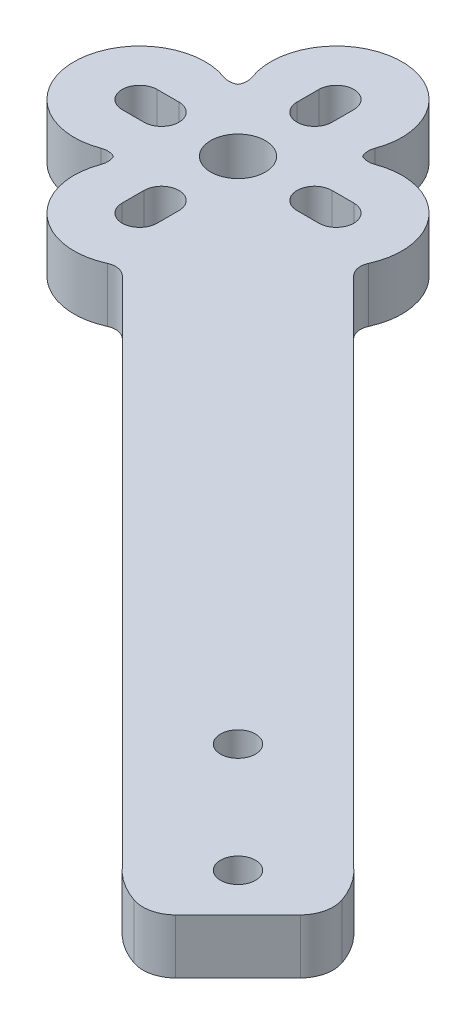
SolidWorks part; units mm, degrees
ref_plane "Front Plane" through (0, 0, 0) normal (0, 0, 1) x (1, 0, 0)
ref_plane "Top Plane" through (0, 0, 0) normal (0, 1, 0) x (1, 0, 0)
ref_plane "Right Plane" through (0, 0, 0) normal (1, 0, 0) x (0, 0, -1)
sketch "Sketch1" plane through (0, 0, 0) normal (0, 1, 0) x (1, 0, 0)
  line L0 (0, 0) -> (79.0685, 79.0685)
  line L1 (-15, 15) -> (15, 15)
  line L2 (-15, 15) -> (-15, -15)
  line L3 (-15, -15) -> (15, -15)
  line L4 (15, 15) -> (15, -15)
  line L5 (-15, 15) -> (15, -15) construction
  line L6 (-15, -15) -> (15, 15) construction
  line L7 (-22.5, 22.5) -> (22.5, 22.5)
  line L8 (-22.5, 22.5) -> (-22.5, -22.5)
  line L9 (-22.5, -22.5) -> (22.5, -22.5)
  line L10 (22.5, 22.5) -> (22.5, -22.5)
  line L11 (-22.5, 22.5) -> (22.5, -22.5) construction
  line L12 (-22.5, -22.5) -> (22.5, 22.5) construction
  line L13 (0, 0) -> (79.0685, -79.0685)
  line L14 (0, 0) -> (-79.0685, -79.0685)
  line L15 (0, 0) -> (-79.0685, 79.0685)
  line L16 (-79.0685, 79.0685) -> (-73.4117, 73.4117)
  line L17 (-79.0685, 88.0685) -> (-79.0685, 86.0685) construction
  line L22 (-77.4685, 88.0685) -> (-77.4685, 86.0685)
  line L25 (-80.6685, 88.0685) -> (-80.6685, 86.0685)
  line L28 (-70.0685, 80.6685) -> (-72.0685, 80.6685)
  line L29 (-22.5, 22.5) -> (-28.1569, 28.1569)
  line L30 (-17.5756, 28.1569) -> (-65.1096, 75.6909)
  line L31 (32.5, 32.5) -> (-32.5, 32.5)
  line L32 (32.5, 32.5) -> (32.5, -32.5)
  line L33 (32.5, -32.5) -> (-32.5, -32.5)
  line L34 (-32.5, 32.5) -> (-32.5, -32.5)
  line L35 (32.5, 32.5) -> (-32.5, -32.5) construction
  line L36 (32.5, -32.5) -> (-32.5, 32.5) construction
  line L37 (-70.0685, 77.4685) -> (-72.0685, 77.4685)
  line L38 (-70.0685, 79.0685) -> (-72.0685, 79.0685) construction
  line L39 (-77.4685, 70.0685) -> (-77.4685, 72.0685)
  line L40 (-80.6685, 70.0685) -> (-80.6685, 72.0685)
  line L41 (-79.0685, 70.0685) -> (-79.0685, 72.0685) construction
  line L42 (-88.0685, 77.4685) -> (-86.0685, 77.4685)
  line L43 (-88.0685, 80.6685) -> (-86.0685, 80.6685)
  line L44 (-88.0685, 79.0685) -> (-86.0685, 79.0685) construction
  line L45 (-28.1569, 17.5756) -> (-75.6909, 65.1096)
  circle A0 centre (79.0685, 79.0685) radius 72.5
  circle A1 centre (79.0685, -79.0685) radius 72.5
  circle A2 centre (-79.0685, -79.0685) radius 72.5
  circle A3 centre (-79.0685, 79.0685) radius 72.5
  circle A4 centre (-79.0685, 79.0685) radius 8
  circle A17 centre (-79.0685, 79.0685) radius 2.5
  circle A18 centre (-32.5, 32.5) radius 1.6
  circle A19 centre (-22.5, 22.5) radius 1.6
  circle A20 centre (-22.5, 22.5) radius 7.5
  arc A21 (-77.4685, 88.0685) -> (-80.6685, 88.0685) centre (-79.0685, 88.0685) ccw
  arc A22 (-80.6685, 86.0685) -> (-77.4685, 86.0685) centre (-79.0685, 86.0685) ccw
  arc A23 (-70.0685, 77.4685) -> (-70.0685, 80.6685) centre (-70.0685, 79.0685) ccw
  arc A24 (-72.0685, 80.6685) -> (-72.0685, 77.4685) centre (-72.0685, 79.0685) ccw
  arc A25 (-80.6685, 70.0685) -> (-77.4685, 70.0685) centre (-79.0685, 70.0685) ccw
  arc A26 (-77.4685, 72.0685) -> (-80.6685, 72.0685) centre (-79.0685, 72.0685) ccw
  arc A27 (-88.0685, 80.6685) -> (-88.0685, 77.4685) centre (-88.0685, 79.0685) ccw
  arc A28 (-86.0685, 77.4685) -> (-86.0685, 80.6685) centre (-86.0685, 79.0685) ccw
  circle A29 centre (-88.0685, 79.0685) radius 6
  circle A30 centre (-79.0685, 88.0685) radius 6
  circle A31 centre (-70.0685, 79.0685) radius 6
  circle A32 centre (-79.0685, 70.0685) radius 6
  point P0 (0, 0)
  point P6 (0, 0)
  point P23 (0, 0)
  point P25 (-79.0685, 87.0685)
  point P36 (-71.0685, 79.0685)
  point P43 (-79.0685, 71.0685)
  point P50 (-87.0685, 79.0685)
  point P54 (-79.0685, 79.0685)
  point P58 (-79.0685, 79.0685)
  point P63 (-79.0685, 79.0685)
  dimension "D3" = 145
  dimension "D6" = 16
  dimension "D7" = 1.6
  dimension "D10" = 12
  dimension "D12" = 5
  dimension "D14" = 3.2
  dimension "D15" = 15
  dimension "D4" = 80
  dimension "D1" = 30
  dimension "D2" = 45
  dimension "D8" = 2
  dimension "D13" = 65
  dimension "D5" = 4
  dimension "D9" = 4
extrude "Boss-Extrude1" add sketch "Sketch1" along normal blind 5 contours A20 L30 L31 A3 | L7 A20 L29 A19 | L29 A20 L8 A19 | L15 A20 L7 A19 | L8 A20 L15 A19 | A20 A3 L34 L45 | A3 L45 L34 | A3 L31 L30 | A31 A4 L15 A18 L31 A3 L30 | A18 L15 L29 A3 L31 | A18 L34 A3 L29 L15 | A32 L45 A3 L34 A18 L15 A4 | A31 A4 L28 A23 L37 | A32 A4 L39 A25 L40 | A4 A32 L40 A26 L39 | A4 A31 L37 A24 L28 | A32 A4 A17 A31 A30 A29 | A4 A30 L22 A22 L25 | A4 A29 L43 A28 L42 | A4 A29 L42 A27 L43 | A4 A30 L25 A21 L22 region at (-20.5654, 0, -17.8296) region at (-17.8296, 0, -20.5654) region at (-20.9432, 0, -26.2585) region at (-26.2585, 0, -20.9432) region at (-22.6251, 0, -30.7123) region at (-30.7123, 0, -22.6251) region at (-22.7348, 0, -32.7889) region at (-30.8653, 0, -27.7242) region at (-27.7242, 0, -30.8653) region at (-32.7889, 0, -22.7348) region at (-47.9912, 0, -53.3493) region at (-53.3493, 0, -47.9912) region at (-68.2689, 0, -79.0685) region at (-79.0685, 0, -68.2689) region at (-73.7862, 0, -79.0685) region at (-73.3339, 0, -73.7391) region at (-79.0685, 0, -73.7862) region at (-89.8682, 0, -79.0685) region at (-84.3509, 0, -79.0685) region at (-79.0685, 0, -84.3509) region at (-79.0685, 0, -89.8682)
fillet "Fillet1" radius 1.5 8 edges at (-75.6909, 2.5, -65.1096) (-65.1096, 2.5, -75.6909) (-73.8407, 2.5, -85.1241) (-73.013, 2.5, -84.2964) (-84.2964, 2.5, -85.1241) (-85.1241, 2.5, -84.2964) (-84.2964, 2.5, -73.013) (-85.1241, 2.5, -73.8407)
sketch "Sketch4" plane through (0, 5, 0) normal (0, 1, 0) x (1, 0, 0)
  line L0 (-22.5, 22.5) -> (-17.1967, 17.1967)
  line L1 (-22.9173, 15.0116) -> (-15.0116, 22.9173)
  arc A0 (-28.1569, 17.5756) -> (-17.5756, 28.1569) centre (-22.5, 22.5) ccw construction
  arc A1 (-22.9173, 15.0116) -> (-15.0116, 22.9173) centre (-22.5, 22.5) ccw
  point P9 (-18.9645, 18.9645)
  arc M15 (-28.1569, 17.5756) -> (-17.5756, 28.1569) centre (-22.5, 22.5) ccw
  dimension "D1" = 5
extrude "Cut-Extrude1" cut sketch "Sketch4" against normal blind 10 contours L1 L0 M15 | L1 L0 M15 region at (-16.7243, 5, -19.7681) region at (-19.7681, 5, -16.7243)
fillet "Fillet2" radius 3 2 edges at (-15.0116, 2.5, -22.9173) (-22.9173, 2.5, -15.0116)
sketch "Sketch5" plane through (0, 0, 0) normal (0, -1, 0) x (1, 0, 0)
  line L0 (-79.0685, -79.0685) -> (-32.5, -32.5)
  line L1 (-70.7021, -64.9103) -> (-42.4178, -36.626)
  line L2 (-70.7021, -64.9103) -> (-65.0452, -70.5671)
  line L3 (-42.4178, -36.626) -> (-36.7609, -42.2828)
  line L4 (-65.0452, -70.5671) -> (-36.7609, -42.2828)
  line L5 (-70.7021, -64.9103) -> (-36.7609, -42.2828) construction
  line L6 (-42.4178, -36.626) -> (-65.0452, -70.5671) construction
  line L7 (-17.5756, -28.1569) -> (-64.3082, -74.8895) construction
  point P4 (-55.7843, -55.7843)
  point P5 (-53.7315, -53.5965)
  dimension "D1" = 40
  dimension "D2" = 3
  dimension "D3" = 8
extrude "Boss-Extrude2" add sketch "Sketch5" along normal blind 5 contours L3 L1 L2 L0 | L2 L4 L3 L0 region at (-55.112, 0, -52.2161) region at (-52.2835, 0, -55.0445)
chamfer "Chamfer1" distance 5 angle 60 1 edges at (-67.8736, -5, -67.7387) first distance on face at (-67.8736, -2.5, -67.7387)
chamfer "Chamfer2" distance 5 angle 60 1 edges at (-39.5894, -5, -39.4544) first distance on face at (-39.5894, -2.5, -39.4544)
